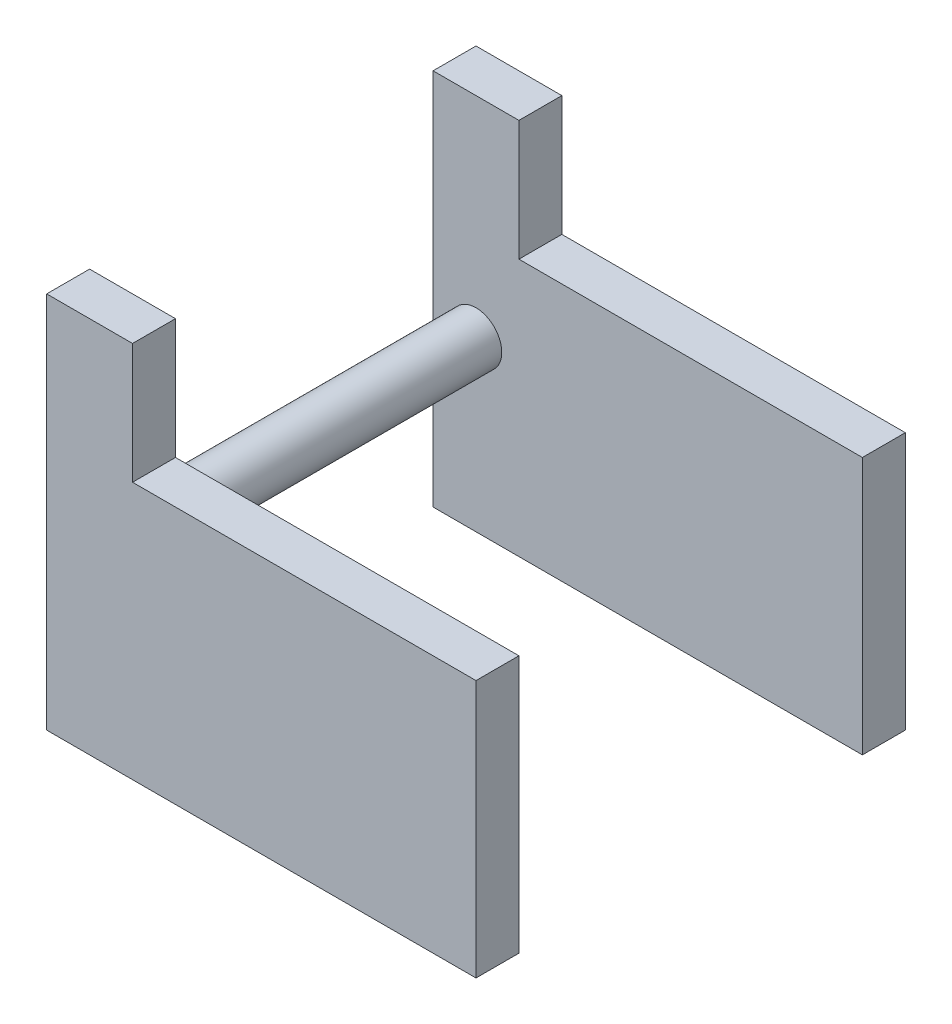
SolidWorks part; units mm, degrees
ref_plane "Front Plane" through (0, 0, 0) normal (0, 0, 1) x (1, 0, 0)
ref_plane "Top Plane" through (0, 0, 0) normal (0, 1, 0) x (1, 0, 0)
ref_plane "Right Plane" through (0, 0, 0) normal (1, 0, 0) x (0, 0, -1)
sketch "Sketch1" plane through (0, 0, 0) normal (0, 0, 1) x (1, 0, 0)
  line L1 (0, 0) -> (-31.75, 0)
  line L2 (0, 0) -> (0, 19.05)
  line L3 (0, 19.05) -> (-25.4, 19.05)
  line L4 (-31.75, 0) -> (-31.75, 6.35)
  line L6 (-31.75, 6.35) -> (-31.75, 27.94)
  line L7 (-31.75, 27.94) -> (-25.4, 27.94)
  line L8 (-25.4, 19.05) -> (-25.4, 27.94)
  dimension "D1" = 31.75
  dimension "D2" = 21.59
  dimension "D3" = 19.05
  dimension "D4" = 6.35
extrude "Boss-Extrude1" add sketch "Sketch1" along normal blind 31.75
sketch "Sketch2" plane through (0, 27.94, 0) normal (0, 1, 0) x (1, 0, 0)
  line L0 (-31.75, -31.75) -> (-31.75, 0) construction
  line L1 (-31.75, -3.175) -> (0, -3.175)
  line L2 (-31.75, -3.175) -> (-31.75, -28.575)
  line L3 (-31.75, -28.575) -> (0, -28.575)
  line L4 (0, -3.175) -> (0, -28.575)
  line L5 (0, -31.75) -> (0, 0) construction
  line L6 (-25.4, -31.75) -> (-31.75, -31.75) construction
  dimension "D1" = 25.4
  dimension "D2" = 3.175
extrude "Cut-Extrude1" cut sketch "Sketch2" against normal up to surface (27.94 mm away) up to face at (-15.875, 0, 15.875)
sketch "Sketch3" plane through (0, 0, 3.175) normal (0, 0, 1) x (1, 0, 0)
  line L0 (-31.75, 0) -> (-31.75, 27.94) construction
  line L2 (-31.75, 0) -> (0, 0) construction
  circle A1 centre (-28.575, 12.446) radius 1.905
  dimension "D4" = 3.81
  dimension "D5" = 12.446
  dimension "D6" = 3.175
extrude "Boss-Extrude2" add sketch "Sketch3" along normal up to surface (25.4 mm away) up to face at (-19.05, 15.6633, 28.575)
